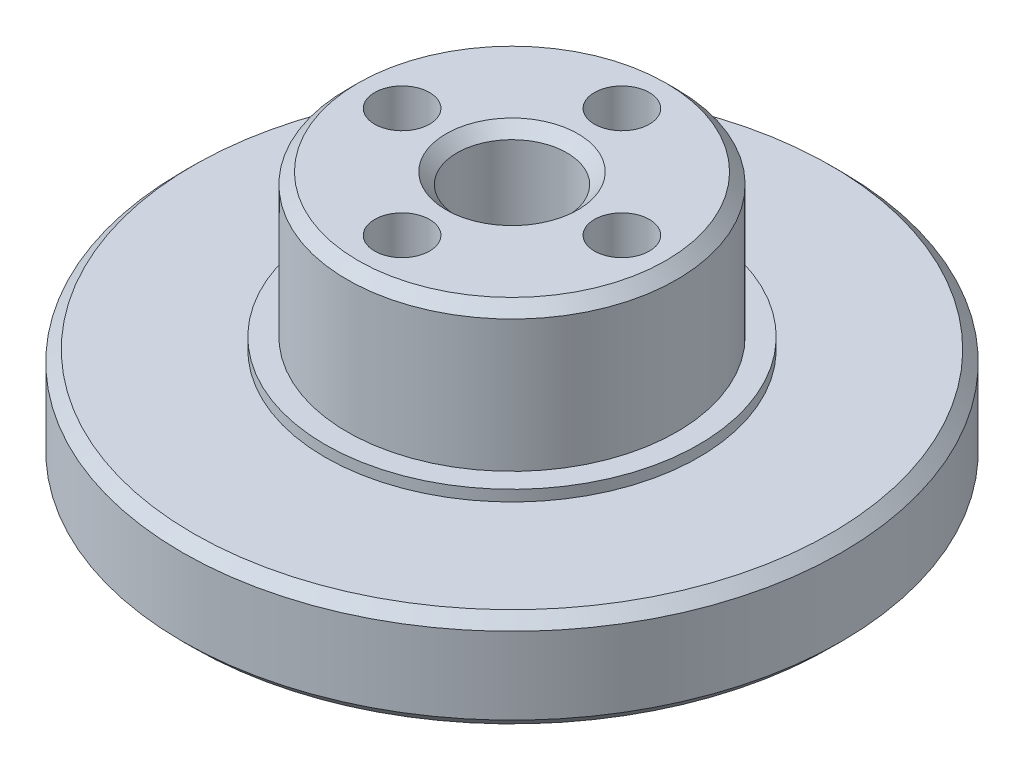
SolidWorks part; units mm, degrees
ref_plane "前视基准面" through (0, 0, 0) normal (0, 0, 1) x (1, 0, 0)
ref_plane "上视基准面" through (0, 0, 0) normal (0, 1, 0) x (1, 0, 0)
ref_plane "右视基准面" through (0, 0, 0) normal (1, 0, 0) x (0, 0, -1)
other "Configuration Table"
sketch "草图1" plane through (0, 0, 0) normal (0, 1, 0) x (1, 0, 0)
  circle A0 centre (0, 0) radius 11.525 construction
  circle A1 centre (0, 11.525) radius 2
  circle A2 centre (9.9809, 5.7625) radius 2
  circle A3 centre (9.9809, -5.7625) radius 2
  circle A4 centre (0, -11.525) radius 2
  circle A5 centre (-9.9809, -5.7625) radius 2
  circle A6 centre (-9.9809, 5.7625) radius 2
  circle A8 centre (0, 0) radius 15
  point P18 (0, 0)
  dimension "D1" = 23.05
  dimension "D2" = 4
  dimension "D5" = 30
  dimension "D3" = 6
extrude "凸台-拉伸1" add sketch "草图1" along normal blind 2.5
sketch "草图2" plane through (0, 2.5, 0) normal (0, 1, 0) x (1, 0, 0)
  circle A0 centre (0, 0) radius 15
extrude "凸台-拉伸2" add sketch "草图2" along normal blind 2
sketch "草图3" plane through (0, 4.5, 0) normal (0, 1, 0) x (1, 0, 0)
  circle A0 centre (0, 0) radius 8.5
  dimension "D1" = 17
extrude "凸台-拉伸3" add sketch "草图3" along normal blind 0.5
sketch "草图4" plane through (0, 5, 0) normal (0, 1, 0) x (1, 0, 0)
  circle A0 centre (0, 0) radius 7.5
  dimension "D1" = 15
extrude "凸台-拉伸4" add sketch "草图4" along normal blind 6.5
sketch "草图5" plane through (0, 11.5, 0) normal (0, 1, 0) x (1, 0, 0)
  circle A0 centre (0, 5) radius 1.25
  circle A1 centre (5, 0) radius 1.25
  circle A2 centre (0, -5) radius 1.25
  circle A3 centre (-5, 0) radius 1.25
  circle A4 centre (0, 0) radius 2.5
  point P12 (0, 0)
  dimension "D1" = 2.5
  dimension "D2" = 5
  dimension "D4" = 5
  dimension "D3" = 4
extrude "切除-拉伸1" cut sketch "草图5" against normal through all
chamfer "倒角1" distance 0.5 angle 45 15 edges at (-9.9809, 0, -3.7625) (-9.9809, 0, 7.7625) (0, 0, 13.525) (9.9809, 0, 7.7625) (9.9809, 0, -3.7625) (0, 0, -9.525) (0, 0, 15) (0, 11.5, 7.5) (0, 4.5, 15) (0, 0, 2.5) (5, 0, 1.25) (0, 0, 6.25) (-5, 0, 1.25) (0, 0, -3.75) (0, 11.5, 2.5)
